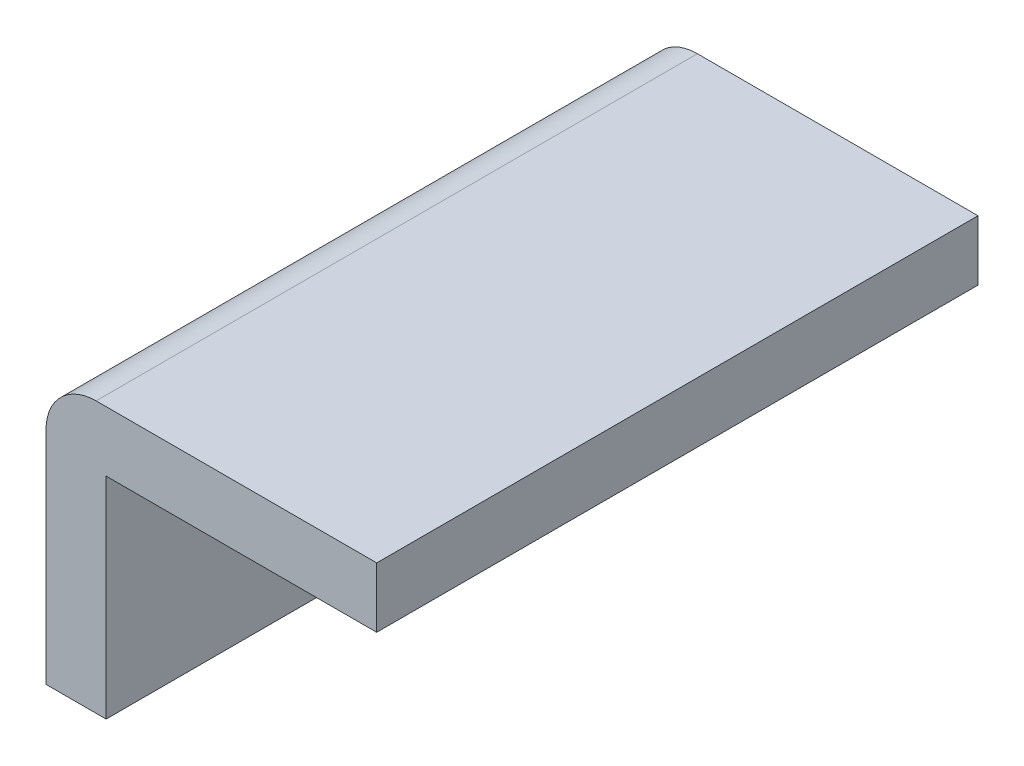
SolidWorks part; units mm, degrees
material "Acrilico TEC"
ref_plane "Front Plane" through (0, 0, 0) normal (0, 0, 1) x (1, 0, 0)
ref_plane "Top Plane" through (0, 0, 0) normal (0, 1, 0) x (1, 0, 0)
ref_plane "Right Plane" through (0, 0, 0) normal (1, 0, 0) x (0, 0, -1)
sketch "Sketch1" plane through (0, 0, 0) normal (0, 0, 1) x (1, 0, 0)
  line L0 (0, 0) -> (0, 11)
  line L1 (1, 12) -> (15, 12)
  line L2 (1.5, 0) -> (1.5, 10.5)
  line L3 (1.5, 10.5) -> (15, 10.5)
  line L4 (-1.5, 0) -> (-1.5, 11)
  line L5 (1, 13.5) -> (15, 13.5)
  line L6 (15, 13.5) -> (15, 10.5)
  line L7 (-1.5, 0) -> (1.5, 0)
  arc A0 (0, 11) -> (1, 12) centre (1, 11) cw
  arc A1 (1.5, 10.5) -> (1.5, 10.5) centre (1.5, 10.5) cw
  arc A2 (-1.5, 11) -> (1, 13.5) centre (1, 11) cw
  point P6 (0, 12)
  dimension "D3" = 1
  dimension "D1" = 15
  dimension "D2" = 12
  dimension "D4" = 1.5
  dimension "D5" = 1.5
extrude "Boss-Extrude1" add sketch "Sketch1" along normal blind 30 contours A0 L0 L7 L2 L3 L6 L1 | A2 L4 L7 L0 A0 L1 L6 L5 region at (-0.75, 0.2132, 0) region at (0.1921, 5.5, 0)
hole_wizard "Ø2.0mm Clearance Dowel Hole1" positions "Sketch2" profile "Sketch3" hole size "Ø2.0" standard "ISO" rebuild error yes end condition through all
sketch "Sketch2" plane through (-35.9294, 10.5, -58.5) normal (0, -1, 0) x (-1, 0, 0)
  point P0 (-26.9294, -76.5)
  point P1 (-26.9294, -70.5)
sketch "Sketch3" plane through (-9, 10.5, 18) normal (1, 0, 0) x (0, 0, -1)
  line L0 (0, 0) -> (0, 3)
  line L1 (0, 3) -> (1, 3)
  line L2 (1, 3) -> (1, 0)
  line L3 (1, 0) -> (0, 0)
  line L4 (0, -6.35) -> (0, 107.95) construction
  dimension "Thru Hole Dia." = 2
  dimension "Thru Hole Depth" = 3
